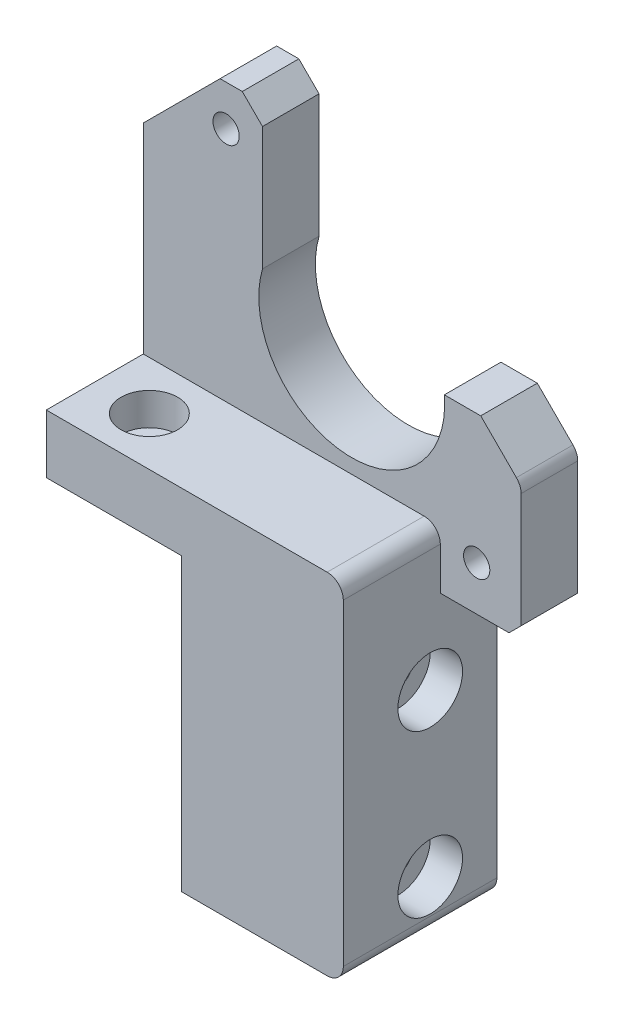
SolidWorks part; units mm, degrees
ref_plane "Front Plane" through (0, 0, 0) normal (0, 0, 1) x (1, 0, 0)
ref_plane "Top Plane" through (0, 0, 0) normal (0, 1, 0) x (1, 0, 0)
ref_plane "Right Plane" through (0, 0, 0) normal (1, 0, 0) x (0, 0, -1)
sketch "Sketch1" plane through (0, 0, 0) normal (0, 0, 1) x (1, 0, 0)
  line L0 (0, 0) -> (20, 0)
  line L1 (20, 0) -> (20, 43.25)
  line L2 (20, 43.25) -> (-16.75, 43.25)
  line L3 (-16.75, 43.25) -> (-16.75, 36)
  line L4 (-16.75, 36) -> (0, 36)
  line L5 (0, 36) -> (0, 0)
  dimension "D1" = 20
  dimension "D2" = 43.25
  dimension "D3" = 16.75
  dimension "D4" = 36
extrude "Boss-Extrude1" add sketch "Sketch1" along normal blind 19
sketch "Sketch2" plane through (0, 0, 0) normal (0, 0, -1) x (-1, 0, 0)
  line L0 (-20, 36) -> (16.75, 36)
  line L1 (16.75, 36) -> (16.75, 68)
  line L2 (16.75, 68) -> (7.25, 77.5)
  line L3 (7.25, 77.5) -> (4.5, 77.5)
  line L4 (4.5, 77.5) -> (2, 75)
  line L5 (2, 75) -> (2, 59.75)
  line L7 (-20, 0) -> (-20, 43.25) construction
  line L8 (-20, 36) -> (-28.5, 36)
  line L9 (-28.5, 36) -> (-30, 37.5)
  line L10 (-30, 37.5) -> (-30, 52.5)
  line L11 (-30, 52.5) -> (-25, 57.5)
  line L12 (-25, 57.5) -> (-20.5, 57.5)
  arc A0 (-20.5, 57.5) -> (2, 59.75) centre (-9.0408, 56.5326) ccw
  dimension "D16" = 23
  dimension "D1" = 45
  dimension "D2" = 32
  dimension "D3" = 9.5
  dimension "D4" = 2.75
  dimension "D5" = 45
  dimension "D6" = 2.5
  dimension "D7" = 15.25
  dimension "D9" = 8.5
  dimension "D10" = 135
  dimension "D11" = 1.5
  dimension "D12" = 15
  dimension "D13" = 45
  dimension "D14" = 5
  dimension "D15" = 4.5
extrude "Boss-Extrude2" add sketch "Sketch2" against normal blind 7
sketch "Sketch3" plane through (20, 0, 0) normal (1, 0, 0) x (0, 0, -1)
  line L0 (0, 0) -> (0, 36) construction
  line L1 (-8.25, 26.25) -> (-8.25, 6.25) construction
  line L2 (-19, 0) -> (0, 0) construction
  circle A0 centre (-8.25, 26.25) radius 1.75
  circle A1 centre (-8.25, 6.25) radius 1.75
  dimension "D4" = 3.5
  dimension "D1" = 8.25
  dimension "D2" = 26.25
  dimension "D3" = 6.25
extrude "Cut-Extrude1" cut sketch "Sketch3" against normal through all
sketch "Sketch6" plane through (20, 0, 0) normal (1, 0, 0) x (0, 0, -1)
  circle A0 centre (-8.25, 26.25) radius 4
  circle A1 centre (-8.25, 6.25) radius 4
  dimension "D1" = 8
extrude "Cut-Extrude4" cut sketch "Sketch6" against normal blind 4
sketch "Sketch7" plane through (0, 0, 0) normal (0, 0, -1) x (-1, 0, 0)
  line L0 (-28.5, 36) -> (-20, 36) construction
  line L1 (-30, 52.5) -> (-30, 37.5) construction
  line L2 (16.75, 36) -> (0, 36) construction
  circle A0 centre (6.5, 72.5) radius 1.625
  circle A1 centre (-24.5, 41.5) radius 1.625
  dimension "D1" = 3.25
  dimension "D2" = 3.25
  dimension "D3" = 5.5
  dimension "D4" = 5.5
  dimension "D5" = 36.5
  dimension "D6" = 36.5
extrude "Cut-Extrude5" cut sketch "Sketch7" against normal through all
fillet "Fillet1" radius 2 3 edges at (20, 43.25, 13) (30, 52.5, 3.5) (20, 0, 9.5)
sketch "Sketch8" plane through (0, 43.25, 0) normal (0, 1, 0) x (1, 0, 0)
  line L0 (-10, -13) -> (-16.75, -13) construction
  line L1 (-16.75, -19) -> (-16.75, -7) construction
  line L2 (-16.75, -7) -> (-16.75, -19) construction
  line L3 (18, -19) -> (-16.75, -19) construction
  circle A0 centre (-10, -13) radius 2
  dimension "D1" = 4
  dimension "D2" = 6.75
  dimension "D3" = 6
extrude "Cut-Extrude6" cut sketch "Sketch8" against normal through all
sketch "Sketch9" plane through (0, 43.25, 0) normal (0, 1, 0) x (1, 0, 0)
  circle A0 centre (-10, -13) radius 3.5
  dimension "D1" = 7
extrude "Cut-Extrude7" cut sketch "Sketch9" against normal blind 4
